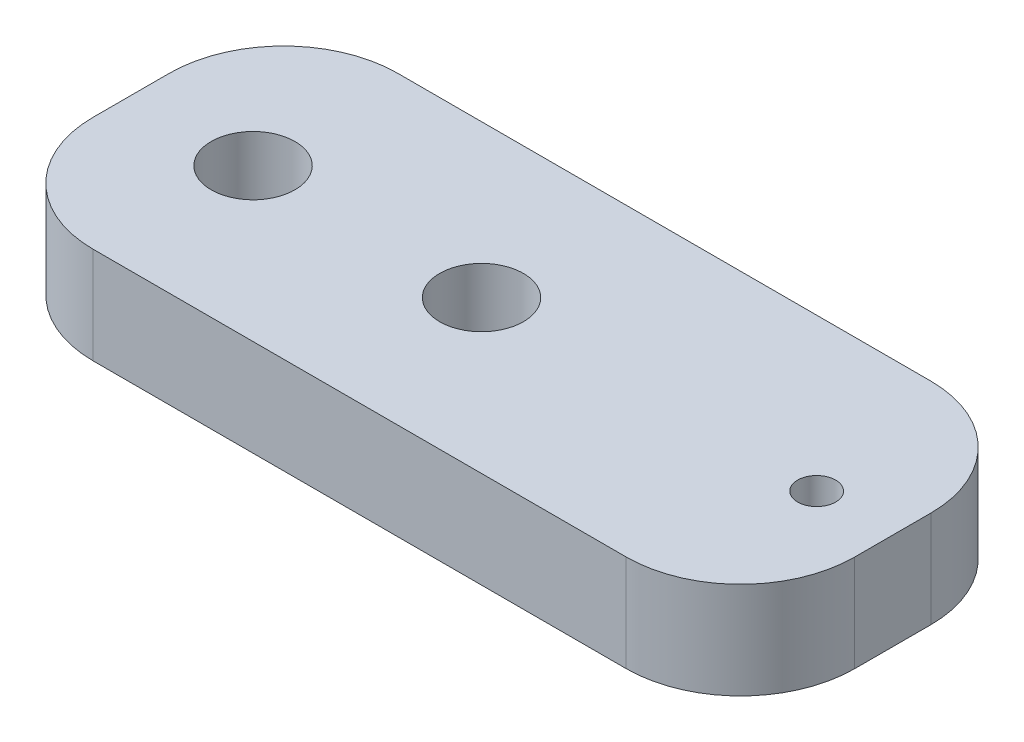
SolidWorks part; units mm, degrees
ref_plane "Front Plane" through (0, 0, 0) normal (0, 0, 1) x (1, 0, 0)
ref_plane "Top Plane" through (0, 0, 0) normal (0, 1, 0) x (1, 0, 0)
ref_plane "Right Plane" through (0, 0, 0) normal (1, 0, 0) x (0, 0, -1)
sketch "Sketch2" plane through (0, 0, 0) normal (0, 1, 0) x (1, 0, 0)
  line L1 (0, 0) -> (50, 0)
  line L2 (0, 0) -> (0, 20)
  line L3 (0, 20) -> (50, 20)
  line L4 (50, 0) -> (50, 20)
  dimension "D1" = 20
  dimension "D2" = 50
extrude "Boss-Extrude1" add sketch "Sketch2" along normal blind 6.35
hole_wizard "M5 Clearance Hole1" positions "3DSketch1" profile "Sketch4" hole size "M5" standard "ANSI Metric" end condition through all
sketch3d "3DSketch1"
  line L0 (0, 6.35, -10) -> (50, 6.35, -10) construction
  line L1 (0, 6.35, -20) -> (0, 6.35, 0) construction
  line L2 (50, 6.35, 0) -> (50, 6.35, -20) construction
  point P7 (8, 6.35, -10)
  point P9 (23, 6.35, -10)
  dimension "D1" = 8
  dimension "D2" = 15
sketch "Sketch4" plane through (8, 6.35, -10) normal (1, 0, 0) x (0, 0, 1)
  line L0 (0, 0) -> (0, 6.35)
  line L1 (0, 6.35) -> (2.75, 6.35)
  line L2 (2.75, 6.35) -> (2.75, 0)
  line L5 (2.75, 0) -> (0, 0)
  line L11 (0, -6.35) -> (0, 107.95) construction
  dimension "Thru Hole Dia." = 5.5
  dimension "Thru Hole Depth" = 6.35
hole_wizard "Tap Drill for M3x0.5 Tap1" positions "3DSketch2" profile "Sketch5" hole size "M3x0.5" standard "ANSI Metric"
sketch3d "3DSketch2"
  line L0 (50, 6.35, -10) -> (0, 6.35, -10) construction
  line L1 (50, 6.35, 0) -> (50, 6.35, -20) construction
  line L2 (0, 6.35, -20) -> (0, 6.35, 0) construction
  point P0 (45, 6.35, -10)
  dimension "D1" = 5
sketch "Sketch5" plane through (45, 6.35, -10) normal (1, 0, 0) x (0, 0, 1)
  line L0 (0, 0) -> (0, 7.1011)
  line L1 (0, 7.1011) -> (1.25, 6.35)
  line L2 (1.25, 6.35) -> (1.25, 0)
  line L5 (1.25, 0) -> (0, 0)
  line L10 (0, 7.1011) -> (-1.25, 6.35) construction
  line L11 (0, -6.35) -> (0, 107.95) construction
  dimension "Hole Dia." = 2.5
  dimension "Hole Depth" = 6.35
  dimension "Drill Angle" = 118
fillet "Fillet1" radius 7.5 4 edges at (50, 3.175, 0) (50, 3.175, -20) (0, 3.175, -20) (0, 3.175, 0)
